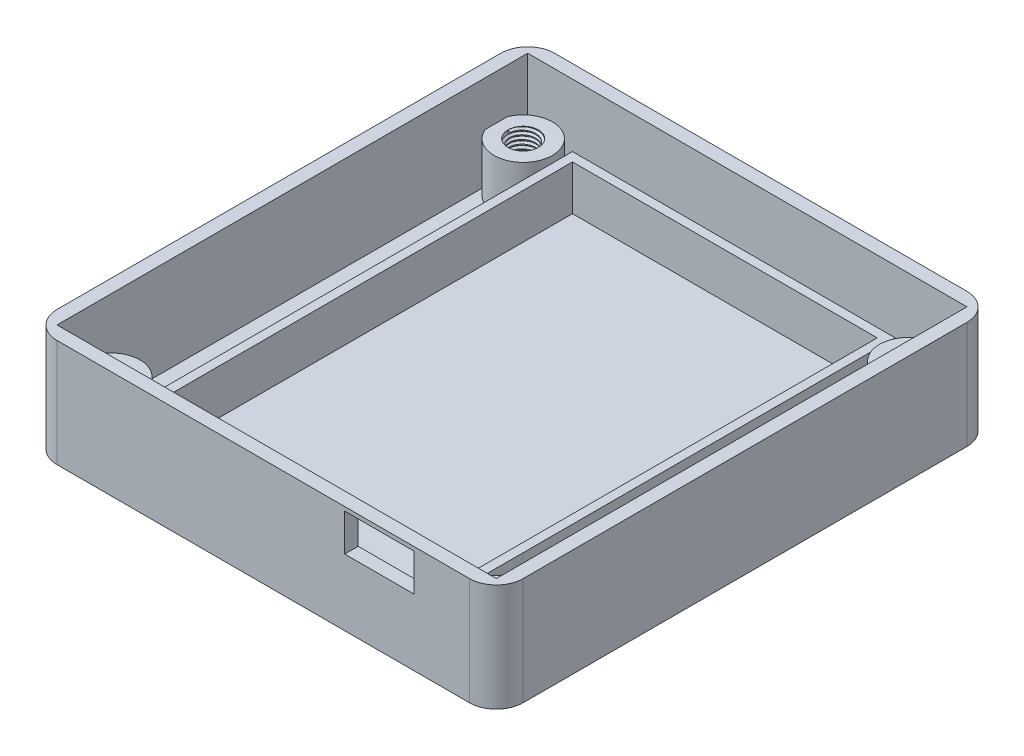
SolidWorks part; units mm, degrees
other "Markup1"
sketch "Sketch18" plane through (0, 20, 0) normal (-0.0248, 0.7832, 0.6212) x (-0.9089, 0.241, -0.3402)
ref_plane "Front Plane" through (0, 0, 0) normal (0, 0, 1) x (1, 0, 0)
ref_plane "Top Plane" through (0, 0, 0) normal (0, 1, 0) x (1, 0, 0)
ref_plane "Right Plane" through (0, 0, 0) normal (1, 0, 0) x (0, 0, -1)
sketch "Sketch1" plane through (0, 0, 0) normal (0, 1, 0) x (1, 0, 0)
  line L1 (0, 0) -> (52, 0)
  line L2 (0, 0) -> (0, 55.5)
  line L3 (0, 55.5) -> (52, 55.5)
  line L4 (52, 0) -> (52, 55.5)
  dimension "D1" = 55.5
  dimension "D2" = 52
extrude "Boss-Extrude1" add sketch "Sketch1" along normal blind 12
sketch "Sketch2" plane through (0, 12, 0) normal (0, 1, 0) x (1, 0, 0)
  line L0 (0, 55.5) -> (0, 0) construction
  line L1 (1.5, 54) -> (50.5, 54)
  line L2 (1.5, 54) -> (1.5, 1.5)
  line L3 (1.5, 1.5) -> (50.5, 1.5)
  line L4 (50.5, 54) -> (50.5, 1.5)
  line L5 (52, 0) -> (52, 55.5) construction
  line L6 (0, 0) -> (52, 0) construction
  line L7 (52, 55.5) -> (0, 55.5) construction
  dimension "D1" = 1.5
  dimension "D2" = 1.5
  dimension "D3" = 1.5
  dimension "D4" = 1.5
extrude "Cut-Extrude1" cut sketch "Sketch2" against normal blind 10.5
sketch "Sketch3" plane through (0, 0, 0) normal (0, -1, 0) x (1, 0, 0)
  line L0 (0, -55.5) -> (0, 0) construction
  line L2 (0, 0) -> (52, 0) construction
  circle A0 centre (4.5, -4.5) radius 3.25
  dimension "D1" = 6.5
  dimension "D2" = 4.5
  dimension "D3" = 4.5
extrude "Boss-Extrude2" add sketch "Sketch3" against normal blind 7
sketch "Sketch6" plane through (0, 7, 0) normal (0, 1, 0) x (1, 0, 0)
  circle A0 centre (4.5, 4.5) radius 1.7
  dimension "D1" = 3.4
extrude "Cut-Extrude4" cut sketch "Sketch6" against normal blind 5
pattern_linear "LPattern1" count 2 spacing 43 along (1, 0, 0) count 2 spacing 46 along (0, 0, -1) of "Cut-Extrude4", "Boss-Extrude2"
fillet "Fillet2" radius 3 4 edges at (0, 6, -55.5) (52, 6, -55.5) (52, 6, 0) (0, 6, 0)
sketch "Sketch7" plane through (0, 1.5, 0) normal (0, 1, 0) x (1, 0, 0)
  line L0 (1.5, 1.5) -> (50.5, 1.5) construction
  line L1 (8, 1.5) -> (44, 1.5)
  line L2 (8, 1.5) -> (8, 52.5)
  line L3 (8, 52.5) -> (44, 52.5)
  line L4 (44, 1.5) -> (44, 52.5)
  line L5 (0, 52.5) -> (0, 3) construction
  dimension "D1" = 36
  dimension "D2" = 51
  dimension "D3" = 8
extrude "Boss-Extrude3" add sketch "Sketch7" along normal blind 5
sketch "Sketch8" plane through (0, 6.5, 0) normal (0, 1, 0) x (1, 0, 0)
  line L0 (8, 1.5) -> (44, 1.5) construction
  line L1 (9, 1.5) -> (43, 1.5)
  line L2 (9, 1.5) -> (9, 51.5)
  line L3 (9, 51.5) -> (43, 51.5)
  line L4 (43, 1.5) -> (43, 51.5)
  line L5 (8, 52.5) -> (8, 1.5) construction
  dimension "D1" = 1
  dimension "D2" = 34
  dimension "D3" = 50
extrude "Cut-Extrude5" cut sketch "Sketch8" against normal blind 5
thread "Thread1" pitch 0.4536 method extrude profile "Thread Profile1" start angle 0, offset 0, length 4, pitch 0.4536, diameter 3.4
ref_plane "Plane1" through (2.8, 7, -50.5) normal (0, 0, 1) x (-1, 0, 0)
sketch "Thread Profile1" plane through (2.8, 7, -50.5) normal (0, 0, 1) x (-1, 0, 0)
  line L0 (0, 0) -> (0, 0.4536) construction
  line L11 (0, 0) -> (0, 0.3969)
  line L12 (0, 0.3969) -> (-0.2455, 0.2551)
  line L13 (-0.2455, 0.2551) -> (-0.2455, 0.1417)
  line L15 (-0.2455, 0.1417) -> (0, 0)
  line L17 (-0.2455, 0.1984) -> (0, 0.1984) construction
  point P2 (0, 0)
  dimension "Pitch" = 0.4536
  dimension "Profile_Angle" = 60
  dimension "Profile_Land" = 0.1134
  dimension "Profile_Height" = 0.2455
thread "Thread2" pitch 0.4536 method extrude profile "Thread Profile2" start angle 0, offset 0, length 4, pitch 0.4536, diameter 3.4
ref_plane "Plane2" through (45.8, 7, -50.5) normal (0, 0, 1) x (-1, 0, 0)
sketch "Thread Profile2" plane through (45.8, 7, -50.5) normal (0, 0, 1) x (-1, 0, 0)
  line L0 (0, 0) -> (0, 0.4536) construction
  line L11 (0, 0) -> (0, 0.3969)
  line L12 (0, 0.3969) -> (-0.2455, 0.2551)
  line L13 (-0.2455, 0.2551) -> (-0.2455, 0.1417)
  line L15 (-0.2455, 0.1417) -> (0, 0)
  line L17 (-0.2455, 0.1984) -> (0, 0.1984) construction
  point P2 (0, 0)
  dimension "Pitch" = 0.4536
  dimension "Profile_Angle" = 60
  dimension "Profile_Land" = 0.1134
  dimension "Profile_Height" = 0.2455
thread "Thread3" pitch 0.4536 method extrude profile "Thread Profile3" start angle 0, offset 0, length 4, pitch 0.4536, diameter 3.4
ref_plane "Plane3" through (2.8, 7, -4.5) normal (0, 0, 1) x (-1, 0, 0)
sketch "Thread Profile3" plane through (2.8, 7, -4.5) normal (0, 0, 1) x (-1, 0, 0)
  line L0 (0, 0) -> (0, 0.4536) construction
  line L11 (0, 0) -> (0, 0.3969)
  line L12 (0, 0.3969) -> (-0.2455, 0.2551)
  line L13 (-0.2455, 0.2551) -> (-0.2455, 0.1417)
  line L15 (-0.2455, 0.1417) -> (0, 0)
  line L17 (-0.2455, 0.1984) -> (0, 0.1984) construction
  point P2 (0, 0)
  dimension "Pitch" = 0.4536
  dimension "Profile_Angle" = 60
  dimension "Profile_Land" = 0.1134
  dimension "Profile_Height" = 0.2455
thread "Thread4" pitch 0.4536 method extrude profile "Thread Profile4" start angle 0, offset 0, length 4, pitch 0.4536, diameter 3.4
ref_plane "Plane4" through (45.8, 7, -4.5) normal (0, 0, 1) x (-1, 0, 0)
sketch "Thread Profile4" plane through (45.8, 7, -4.5) normal (0, 0, 1) x (-1, 0, 0)
  line L0 (0, 0) -> (0, 0.4536) construction
  line L11 (0, 0) -> (0, 0.3969)
  line L12 (0, 0.3969) -> (-0.2455, 0.2551)
  line L13 (-0.2455, 0.2551) -> (-0.2455, 0.1417)
  line L15 (-0.2455, 0.1417) -> (0, 0)
  line L17 (-0.2455, 0.1984) -> (0, 0.1984) construction
  point P2 (0, 0)
  dimension "Pitch" = 0.4536
  dimension "Profile_Angle" = 60
  dimension "Profile_Land" = 0.1134
  dimension "Profile_Height" = 0.2455
sketch "Sketch21" plane through (0, 0, 0) normal (0, 0, 1) x (1, 0, 0)
  line L0 (3, 12) -> (49, 12) construction
  line L1 (35.09, 11.56) -> (42.79, 11.56)
  line L2 (35.09, 11.56) -> (35.09, 7.41)
  line L3 (35.09, 7.41) -> (42.79, 7.41)
  line L4 (42.79, 11.56) -> (42.79, 7.41)
  line L5 (50.5, 1.5) -> (50.5, 12) construction
  dimension "D1" = 0.44
  dimension "D2" = 7.7
  dimension "D3" = 4.15
  dimension "D4" = 7.71
extrude "Cut-Extrude6" cut sketch "Sketch21" against normal blind 2
